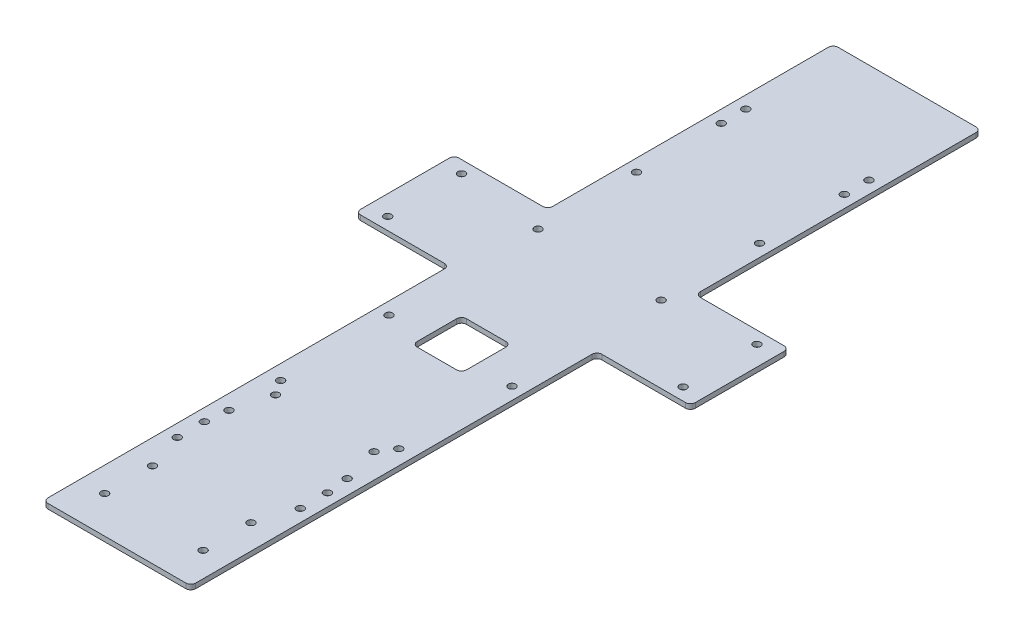
SolidWorks part; units mm, degrees
ref_plane "Спереди" through (0, 0, 0) normal (0, 0, 1) x (1, 0, 0)
ref_plane "Сверху" through (0, 0, 0) normal (0, 1, 0) x (1, 0, 0)
ref_plane "Справа" through (0, 0, 0) normal (1, 0, 0) x (0, 0, -1)
sketch "компоновка" plane through (0, 0, 0) normal (0, 1, 0) x (1, 0, 0)
  line L0 (-25, -130) -> (25, -130) construction
  line L1 (-25, -124.35) -> (25, -124.35) construction
  line L2 (-25, -124.35) -> (-25, -135.65) construction
  line L3 (-25, -135.65) -> (25, -135.65) construction
  line L4 (25, -124.35) -> (25, -135.65) construction
  line L5 (-7, -135.65) -> (7, -135.65) construction
  line L6 (-7, -135.65) -> (-7, -140.75) construction
  line L7 (-7, -140.75) -> (7, -140.75) construction
  line L8 (7, -135.65) -> (7, -140.75) construction
  line L9 (0, -124.35) -> (0, -135.65) construction
  line L10 (-18, -141.8192) -> (18, -29.3192) construction
  line L11 (-18, -141.8192) -> (-18, -29.3192) construction
  line L12 (-18, -141.8192) -> (18, -141.8192) construction
  line L13 (18, -141.8192) -> (18, -29.3192) construction
  line L14 (-18, -29.3192) -> (18, -29.3192) construction
  line L15 (-6.5, -173.0692) -> (-6.5, -141.8192) construction
  line L16 (-6.5, -173.0692) -> (6.5, -173.0692) construction
  line L17 (6.5, -173.0692) -> (6.5, -141.8192) construction
  line L18 (-6.5, -141.8192) -> (6.5, -141.8192) construction
  line L19 (20, -110.5692) -> (-20, -60.5692) construction
  line L20 (20, -110.5692) -> (20, -60.5692) construction
  line L21 (20, -110.5692) -> (-20, -110.5692) construction
  line L22 (-20, -110.5692) -> (-20, -60.5692) construction
  line L23 (20, -60.5692) -> (-20, -60.5692) construction
  line L24 (-27.5, -42.5) -> (27.5, -87.5) construction
  line L25 (-27.5, -42.5) -> (27.5, -42.5) construction
  line L26 (-27.5, -42.5) -> (-27.5, -87.5) construction
  line L27 (-27.5, -87.5) -> (27.5, -87.5) construction
  line L28 (27.5, -42.5) -> (27.5, -87.5) construction
  line L29 (-25, 91.0749) -> (25, 91.0749) construction
  line L30 (-25, 91.0749) -> (-25, 51.0749) construction
  line L31 (-25, 51.0749) -> (25, 51.0749) construction
  line L32 (25, 91.0749) -> (25, 51.0749) construction
  line L33 (-25, 51.0749) -> (25, 91.0749) construction
  line L34 (-24, -54.5) -> (24, -75.5) construction
  line L35 (-24, -54.5) -> (24, -54.5) construction
  line L36 (-24, -54.5) -> (-24, -75.5) construction
  line L37 (-24, -75.5) -> (24, -75.5) construction
  line L38 (24, -54.5) -> (24, -75.5) construction
  line L39 (-24, -65) -> (24, -65) construction
  line L40 (-27.5, -65) -> (27.5, -65) construction
  circle A0 centre (-20, -130) radius 1.5
  circle A1 centre (20, -130) radius 1.5
  circle A2 centre (-24, -54.5) radius 1.5
  circle A3 centre (24, -54.5) radius 1.5
  circle A4 centre (-20, -110.5692) radius 1.5
  circle A5 centre (-20, -60.5692) radius 1.5
  circle A6 centre (20, -60.5692) radius 1.5
  circle A7 centre (20, -110.5692) radius 1.5
  circle A8 centre (-25, 91.0749) radius 1.5
  circle A9 centre (25, 91.0749) radius 1.5
  circle A10 centre (25, 51.0749) radius 1.5
  circle A11 centre (-25, 51.0749) radius 1.5
  circle A12 centre (24, -75.5) radius 1.5
  circle A13 centre (-24, -75.5) radius 1.5
  point P13 (0, -135.65)
  point P14 (0, -135.65)
  point P29 (0, -85.5692)
  point P30 (0, -85.5692)
  point P43 (0, -65)
  point P57 (0, -130)
  point P67 (0, -65)
  point P79 (0, -141.8192)
  point P80 (0, -141.8192)
  point P88 (0, 71.0749)
  dimension "D3" = 50
  dimension "D7" = 3
  dimension "D18" = 3
  dimension "D23" = 3
  dimension "D27" = 3
  dimension "D4" = 40
  dimension "D5" = 11.3
  dimension "D6" = 16.4
  dimension "D8" = 50
  dimension "D9" = 40
  dimension "D10" = 112.5
  dimension "D11" = 13
  dimension "D12" = 31.25
  dimension "D13" = 36
  dimension "D14" = 55
  dimension "D15" = 45
  dimension "D16" = 50
  dimension "D17" = 40
  dimension "D19" = 65
  dimension "D21" = 14
  dimension "D22" = 65
  dimension "D24" = 48
  dimension "D25" = 21
  dimension "D26" = 130
sketch "Эскиз1" plane through (0, 0, 0) normal (0, 1, 0) x (1, 0, 0)
  line L0 (0, 176) -> (0, -145) construction
  line L1 (-30, 176) -> (30, 176)
  line L2 (-30, 176) -> (-30, -145)
  line L3 (-30, -145) -> (30, -145)
  line L4 (30, 176) -> (30, -145)
  line L5 (-30, 0) -> (30, 0) construction
  dimension "D1" = 60
  dimension "D2" = 176
  dimension "D3" = 145
extrude "тело" add sketch "Эскиз1" along normal blind 2
sketch "Эскиз3" plane through (0, 2, 0) normal (0, 1, 0) x (1, 0, 0)
  line L0 (0, 176) -> (0, -145) construction
  line L1 (30, 176) -> (-30, 176) construction
  line L2 (-30, -145) -> (30, -145) construction
  line L3 (-30, 176) -> (-30, -145) construction
  line L4 (-30, 60) -> (-68, 60)
  line L5 (-30, 60) -> (-30, 20)
  line L6 (-30, 20) -> (-68, 20)
  line L7 (-68, 60) -> (-68, 20)
  line L8 (30, -145) -> (30, 176) construction
  line L9 (30, 60) -> (68, 60)
  line L10 (30, 60) -> (30, 20)
  line L11 (30, 20) -> (68, 20)
  line L12 (68, 60) -> (68, 20)
  line L13 (-68, 40) -> (68, 40) construction
  dimension "D1" = 40
  dimension "D2" = 40
  dimension "D3" = 68
sketch "Эскиз4" plane through (0, 2, 0) normal (0, 1, 0) x (1, 0, 0)
  line L0 (0, 176) -> (0, -145) construction
  line L1 (-60, 55) -> (-60, 25) construction
  line L2 (60, 55) -> (60, 25) construction
  line L3 (-60, 40) -> (60, 40) construction
  circle A0 centre (-60, 55) radius 1.5
  circle A1 centre (-60, 25) radius 1.5
  circle A2 centre (60, 55) radius 1.5
  circle A3 centre (60, 25) radius 1.5
  point P15 (0, 40)
  dimension "D1" = 3
  dimension "D2" = 30
  dimension "D3" = 60
  dimension "D4" = 40
extrude "уши крепления подвески" add sketch "Эскиз3" against normal up to surface (2 mm away) up to face at (0, 0, -15.5)
extrude "крепление подвески" cut sketch "Эскиз4" against normal through all
sketch "Эскиз6" plane through (0, 2, 0) normal (0, 1, 0) x (1, 0, 0)
  circle A0 centre (-20, -60.5692) radius 1.5
  circle A1 centre (20, -60.5692) radius 1.5
  circle A2 centre (20, -110.5692) radius 1.5
  circle A3 centre (-20, -110.5692) radius 1.5
  dimension "D1" = 3
extrude "крепление bullet" cut sketch "Эскиз6" against normal through all
sketch "Эскиз7" plane through (0, 2, 0) normal (0, 1, 0) x (1, 0, 0)
  circle A0 centre (-25, 91.0749) radius 1.5
  circle A1 centre (25, 91.0749) radius 1.5
  circle A2 centre (25, 51.0749) radius 1.5
  circle A3 centre (-25, 51.0749) radius 1.5
  dimension "D1" = 3
extrude "крепление платы серв" cut sketch "Эскиз7" against normal through all
sketch "Эскиз8" plane through (0, 2, 0) normal (0, 1, 0) x (1, 0, 0)
  circle A0 centre (-20, -130) radius 1.5
  circle A1 centre (20, -130) radius 1.5
  dimension "D1" = 3
extrude "крепление камеры" cut sketch "Эскиз8" against normal through all and the other way through all
sketch "Эскиз9" plane through (0, 2, 0) normal (0, 1, 0) x (1, 0, 0)
  circle A0 centre (-24, -54.5) radius 1.5
  circle A1 centre (24, -54.5) radius 1.5
  circle A2 centre (24, -75.5) radius 1.5
  circle A3 centre (-24, -75.5) radius 1.5
  dimension "D1" = 3
extrude "плата раздачи питания" cut sketch "Эскиз9" against normal through all
sketch "Эскиз11" plane through (0, 2, 0) normal (0, 1, 0) x (1, 0, 0)
  line L0 (0, 176) -> (0, -145) construction
  line L1 (30, 176) -> (-30, 176) construction
  line L2 (-30, -145) -> (30, -145) construction
  line L3 (-30, 15.5) -> (30, 15.5) construction
  line L6 (-25, 135.5) -> (25, 135.5) construction
  line L7 (-25, -95.5) -> (25, -95.5) construction
  line L8 (-30, 20) -> (-30, -145) construction
  line L9 (30, -145) -> (30, 20) construction
  circle A0 centre (-25, 135.5) radius 1.5
  circle A1 centre (25, 135.5) radius 1.5
  circle A2 centre (-25, -95.5) radius 1.5
  circle A3 centre (25, -95.5) radius 1.5
  point P21 (0, -95.5)
  point P22 (0, 135.5)
  point P23 (0, 15.5)
  dimension "D1" = 3
  dimension "D2" = 50
  dimension "D3" = 120
  dimension "D4" = 111
extrude "крепление нижнего этажа" cut sketch "Эскиз11" against normal through all
sketch "Эскиз13" plane through (0, 2, 0) normal (0, 1, 0) x (1, 0, 0)
  line L0 (-10, -5) -> (10, -5) construction
  line L1 (-10, 5) -> (10, 5)
  line L2 (-10, 5) -> (-10, -15)
  line L3 (-10, -15) -> (10, -15)
  line L4 (10, 5) -> (10, -15)
  point P6 (0, -5)
  dimension "D1" = 20
  dimension "D2" = 20
  dimension "D3" = 5
extrude "отверстие для проводов" cut sketch "Эскиз13" against normal through all
sketch "Эскиз15" plane through (0, 2, 0) normal (0, 1, 0) x (1, 0, 0)
  line L0 (0, 176) -> (0, -145) construction
  line L1 (-25, 125.5) -> (25, 125.5) construction
  line L2 (-25, -9.5) -> (25, -9.5) construction
  line L3 (-25, -84.5) -> (25, -84.5) construction
  line L5 (30, 176) -> (-30, 176) construction
  line L6 (-30, -145) -> (30, -145) construction
  line L8 (-30, 15.5) -> (30, 15.5) construction
  line L10 (-30, 20) -> (-30, -145) construction
  line L11 (30, -145) -> (30, 20) construction
  circle A0 centre (-25, 125.5) radius 1.5
  circle A1 centre (25, 125.5) radius 1.5
  circle A2 centre (25, -84.5) radius 1.5
  circle A3 centre (-25, -84.5) radius 1.5
  circle A4 centre (25, -9.5) radius 1.5
  circle A5 centre (-25, -9.5) radius 1.5
  point P20 (0, 15.5)
  point P21 (0, 15.5)
  point P22 (0, 125.5)
  point P23 (0, -84.5)
  point P28 (0, -9.5)
  dimension "D1" = 3
  dimension "D5" = 3
  dimension "D2" = 50
  dimension "D3" = 110
  dimension "D4" = 100
  dimension "D6" = 25
extrude "крепление уголков" cut sketch "Эскиз15" against normal through all
fillet "Скругление1" radius 2 12 edges at (30, 1, -20) (68, 1, -20) (68, 1, -60) (30, 1, -60) (30, 1, -176) (-30, 1, -176) (-30, 1, -60) (-68, 1, -60) (-68, 1, -20) (-30, 1, -20) (-30, 1, 145) (30, 1, 145)
fillet "Скругление2" radius 2 4 edges at (-10, 1, 15) (10, 1, 15) (10, 1, -5) (-10, 1, -5)
